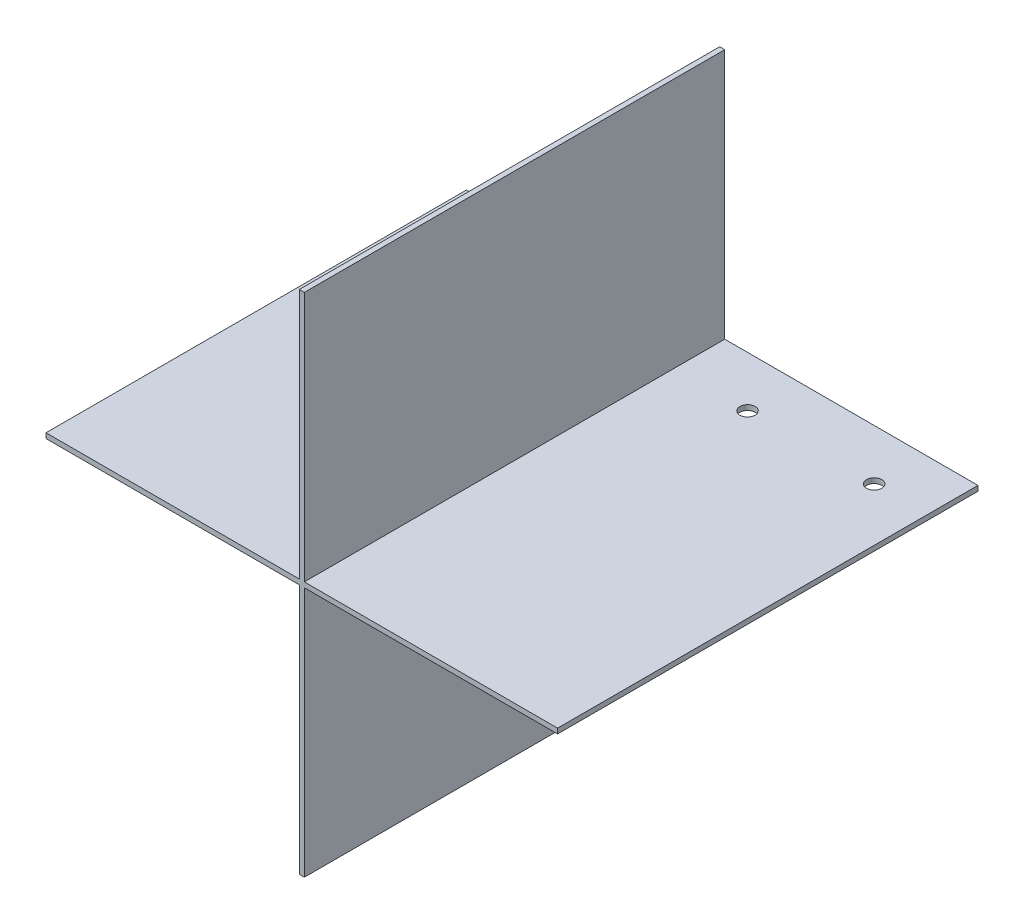
SolidWorks part; units mm, degrees
ref_plane "Front Plane" through (0, 0, 0) normal (0, 0, 1) x (1, 0, 0)
ref_plane "Top Plane" through (0, 0, 0) normal (0, 1, 0) x (1, 0, 0)
ref_plane "Right Plane" through (0, 0, 0) normal (1, 0, 0) x (0, 0, -1)
sketch "Sketch1" plane through (0, 0, 0) normal (1, 0, 0) x (0, 0, -1)
  line L1 (-41.5, 50) -> (41.5, 50)
  line L2 (-41.5, 50) -> (-41.5, -50)
  line L3 (-41.5, -50) -> (41.5, -50)
  line L4 (41.5, 50) -> (41.5, -50)
  line L5 (0, -50) -> (0, 50) construction
  line L6 (-41.5, 0) -> (41.5, 0) construction
  point P0 (0, 0)
  dimension "D1" = 100
  dimension "D2" = 83
extrude "Boss-Extrude1" add sketch "Sketch1" along normal blind 0.5 and the other way blind 0.5
sketch "Sketch2" plane through (0.5, 0, 0) normal (1, 0, 0) x (0, 0, -1)
  line L1 (-41.5, 0.5) -> (41.5, 0.5)
  line L2 (-41.5, 0.5) -> (-41.5, -0.5)
  line L3 (-41.5, -0.5) -> (41.5, -0.5)
  line L4 (41.5, 0.5) -> (41.5, -0.5)
  line L5 (0, -0.5) -> (0, 0.5) construction
  line L6 (-41.5, 0) -> (41.5, 0) construction
  point P0 (0, 0)
  dimension "D1" = 1
  dimension "D2" = 83
extrude "Boss-Extrude2" add sketch "Sketch2" along normal blind 50 and the other way blind 51
sketch "Sketch3" plane through (0, 0.5, 0) normal (0, 1, 0) x (1, 0, 0)
  circle A0 centre (15, 31.5) radius 1.5
  circle A1 centre (40, 31.5) radius 1.5
  circle A2 centre (-40, 31.5) radius 1.5
  circle A3 centre (-15, 31.5) radius 1.5
extrude "Cut-Extrude1" cut sketch "Sketch3" against normal up to next
